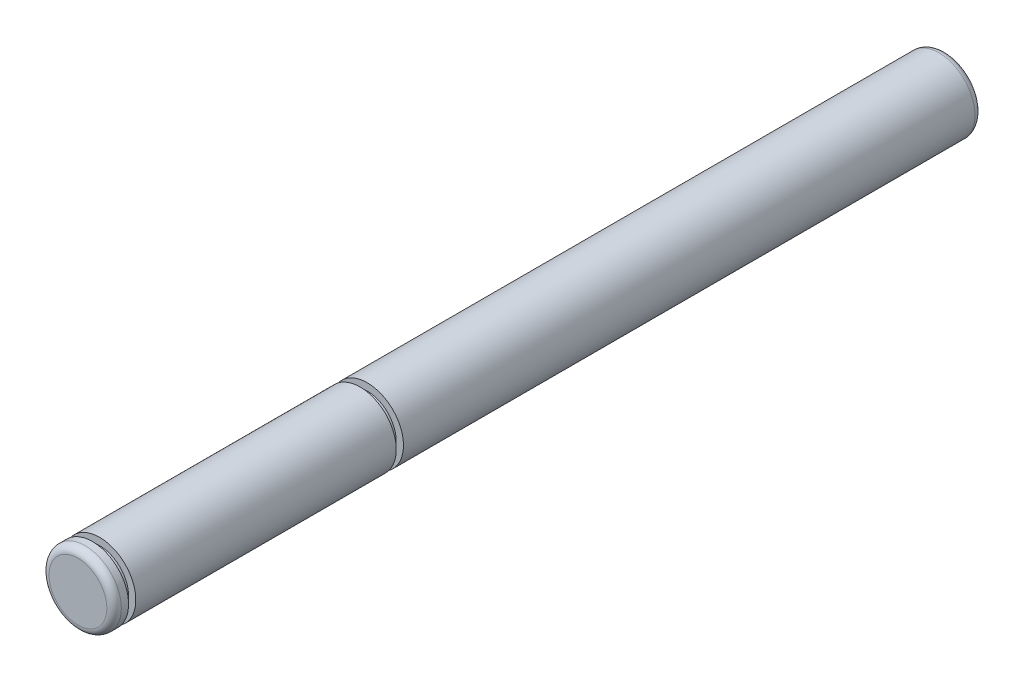
SolidWorks part; units mm, degrees
material "AISI 4340 Steel, normalized"
ref_plane "Front Plane" through (0, 0, 0) normal (0, 0, 1) x (1, 0, 0)
ref_plane "Top Plane" through (0, 0, 0) normal (0, 1, 0) x (1, 0, 0)
ref_plane "Right Plane" through (0, 0, 0) normal (1, 0, 0) x (0, 0, -1)
sketch "Sketch1" plane through (0, 0, 0) normal (0, 0, 1) x (1, 0, 0)
  circle A0 centre (0, 0) radius 2.5
  dimension "D1" = 5
extrude "Boss-Extrude1" add sketch "Sketch1" along normal mid plane 60
sketch "Sketch2" plane through (0, 0, 0) normal (0, 1, 0) x (1, 0, 0)
  line L0 (-2.5, 30) -> (-2.5, -30) construction
  line L1 (-2.5, -29) -> (-2, -29)
  line L2 (-2.5, -29) -> (-2.5, -28.5)
  line L3 (-2.5, -28.5) -> (-2, -28.5)
  line L4 (-2, -29) -> (-2, -28.5)
  line L5 (-2.5, -30) -> (2.5, -30) construction
  line L6 (0, 0) -> (0, -30) construction
  line L7 (-2.5, -10.5) -> (-2, -10.5)
  line L8 (-2.5, -10.5) -> (-2.5, -10)
  line L9 (-2.5, -10) -> (-2, -10)
  line L10 (-2, -10.5) -> (-2, -10)
  dimension "D1" = 0.5
  dimension "D2" = 1
  dimension "D3" = 18
revolve "Cut-Revolve1" cut sketch "Sketch2" angle 360 about L6
fillet "Fillet1" radius 0.5 2 edges at (2.5, 0, -30) (2.5, 0, 30)
